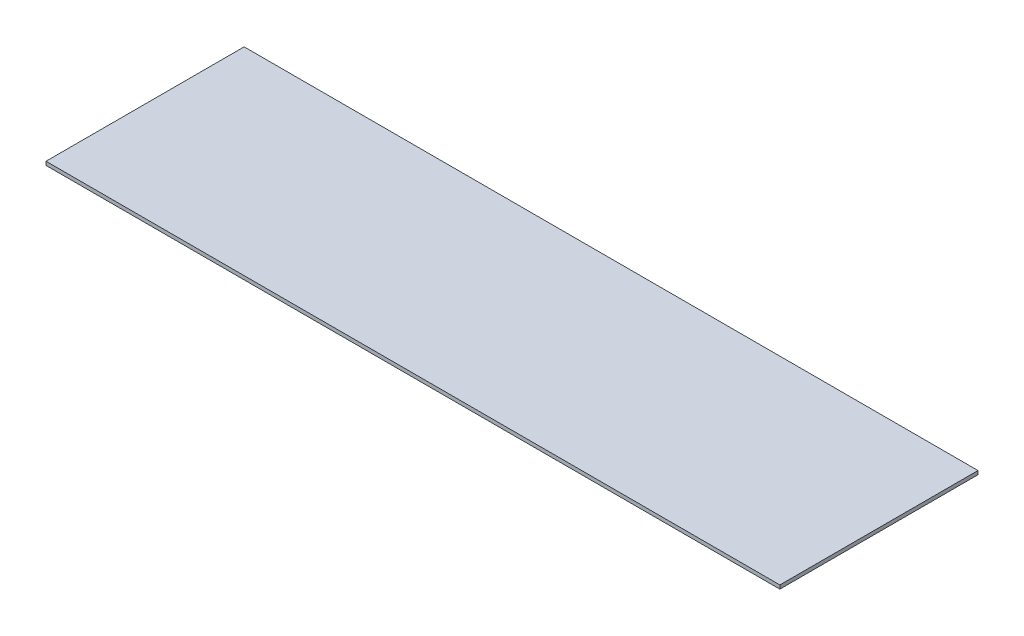
SolidWorks part; units mm, degrees
ref_plane "Front Plane" through (0, 0, 0) normal (0, 0, 1) x (1, 0, 0)
ref_plane "Top Plane" through (0, 0, 0) normal (0, 1, 0) x (1, 0, 0)
ref_plane "Right Plane" through (0, 0, 0) normal (1, 0, 0) x (0, 0, -1)
sketch "Sketch1" plane through (0, 0, 0) normal (0, 1, 0) x (1, 0, 0)
  line L1 (-158.0622, 57.222) -> (476.9378, 57.222)
  line L2 (-158.0622, 57.222) -> (-158.0622, -114.228)
  line L3 (-158.0622, -114.228) -> (476.9378, -114.228)
  line L4 (476.9378, 57.222) -> (476.9378, -114.228)
  dimension "D1" = 171.45
  dimension "D2" = 635
extrude "Boss-Extrude1" add sketch "Sketch1" along normal blind 3.175
